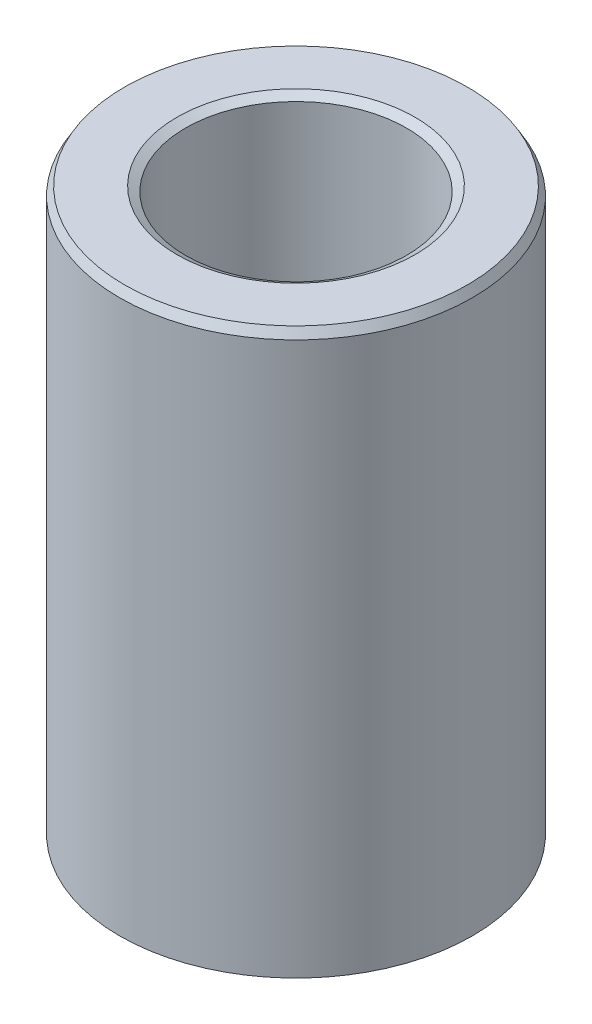
SolidWorks part; units mm, degrees
ref_plane "Front Plane" through (0, 0, 0) normal (0, 0, 1) x (1, 0, 0)
ref_plane "Top Plane" through (0, 0, 0) normal (0, 1, 0) x (1, 0, 0)
ref_plane "Right Plane" through (0, 0, 0) normal (1, 0, 0) x (0, 0, -1)
sketch "Sketch1" plane through (0, 0, 0) normal (0, 1, 0) x (1, 0, 0)
  circle A0 centre (0, 0) radius 27.5
  dimension "SLEEVE_OD" = 55
extrude "Boss-Extrude1" add sketch "Sketch1" along normal blind 88.2808
sketch "Sketch2" plane through (0, 0, 0) normal (0, 1, 0) x (1, 0, 0)
  circle A0 centre (0, 0) radius 17.2209
  dimension "BORE_D" = 34.4418
extrude "Cut-Extrude1" cut sketch "Sketch2" along normal through all
chamfer "Chamfer1" distance 1.3451 angle 30 4 edges at (0, 88.2808, 17.2209) (0, 0, 17.2209) (0, 0, 27.5) (0, 88.2808, 27.5) first distance on face at (0, 88.2808, 17.2209) first distance on face at (0, 0, 17.2209) first distance on face at (0, 88.2808, 27.5)
